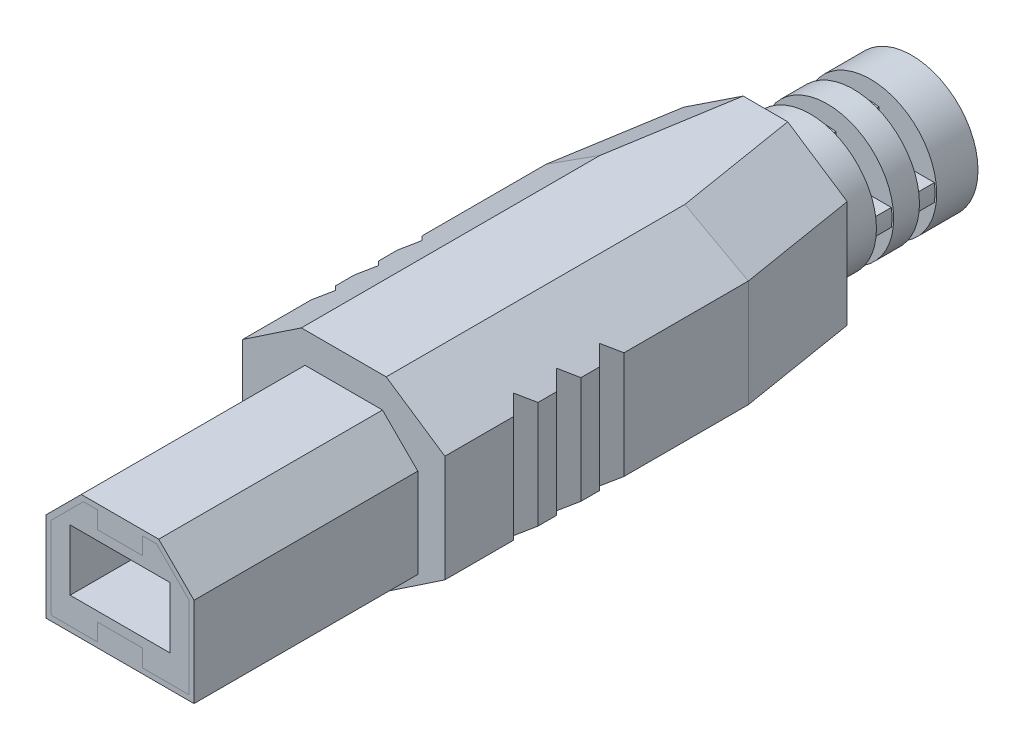
SolidWorks part; units mm, degrees
ref_plane "Front" through (0, 0, 0) normal (0, 0, 1) x (1, 0, 0)
ref_plane "Top" through (0, 0, 0) normal (0, 1, 0) x (1, 0, 0)
ref_plane "Right" through (0, 0, 0) normal (1, 0, 0) x (0, 0, -1)
sketch "Sketch1" plane through (0, 0, 0) normal (0, 0, 1) x (1, 0, 0)
  line L5 (0, 0) -> (-4.3, 0)
  line L6 (-4.3, 0) -> (-4.3, 5.2)
  line L10 (-4.3, 5.2) -> (-2.25, 7.25)
  line L11 (-2.25, 7.25) -> (0, 7.25)
  line L12 (0, 7.25) -> (0, 0)
  line L13 (0, 5.395) -> (-2.9, 5.395)
  line L14 (-2.9, 5.395) -> (-2.9, 1.855)
  line L15 (-2.9, 1.855) -> (0, 1.855)
  line L16 (0, 5.95) -> (-1.3, 5.95)
  line L17 (-1.3, 5.95) -> (-1.3, 6.95)
  line L18 (0, 1.3) -> (-1.3, 1.3)
  line L19 (-1.3, 1.3) -> (-1.3, 0.3)
  line L20 (-2.1257, 6.95) -> (-1.3, 6.95)
  line L21 (-0.3, 6.95) -> (-0.3, 0.3) construction
  line L22 (-1.3, 0.3) -> (-4, 0.3)
  line L23 (-4, 0.3) -> (-4, 5.0757)
  line L24 (-4, 5.0757) -> (-2.1257, 6.95)
  line L25 (-0.3, 0.3) -> (-4, 0.3) construction
  line L26 (-2.1257, 6.95) -> (-0.3, 6.95) construction
  line L27 (-1.3, 6.95) -> (-0.3, 6.95) construction
  line L28 (-1.3, 1.3) -> (-1.3, 1.855)
  line L29 (-0.3, 0.3) -> (-1.3, 0.3) construction
  line L31 (-1.3, 5.395) -> (-1.3, 5.95)
  dimension "D1" = 0.3
  dimension "D2" = 1.3
  dimension "D4" = 3.54
  dimension "D3" = 1.3
  dimension "D5" = 2.9
  dimension "D6" = 7.25
  dimension "D7" = 4.3
  dimension "D8" = 225
  dimension "D9" = 2.25
extrude "Boss-Extrude1" add sketch "Sketch1" against normal blind 13 contours L13 L31 L17 L20 L24 L23 L22 L19 L28 L15 L14 | L28 L18 L12 L15 | L23 L24 L20 L17 L16 L12 L11 L10 L6 L5 L18 L19 L22 | L31 L13 L12 L16
sketch "Sketch2" plane through (0, 0, 0) normal (0, 0, 1) x (1, 0, 0)
  line L0 (0, 5.95) -> (-1.3, 5.95)
  line L1 (-1.3, 5.95) -> (-1.3, 6.95)
  line L2 (-1.3, 6.95) -> (-2.1257, 6.95)
  line L3 (-2.1257, 6.95) -> (-4, 5.0757)
  line L4 (-4, 5.0757) -> (-4, 0.3)
  line L5 (-4, 0.3) -> (-1.3, 0.3)
  line L6 (-1.3, 0.3) -> (-1.3, 1.3)
  line L7 (-1.3, 1.3) -> (0, 1.3)
split line "Split Line4"
mirror "Mirror1" about plane through (0, 0, -13) normal (-1, 0, 0) of bodies 115
sketch "Sketch3" plane through (0, 0, -13) normal (0, 0, -1) x (-1, 0, 0)
  line L0 (-5.875, 7.125) -> (-3.0438, 9.025) construction
  line L1 (-3.0438, 9.025) -> (3.0438, 9.025)
  line L2 (-5.875, 7.125) -> (-5.875, 0.125)
  line L3 (-3.0438, -1.775) -> (3.0438, -1.775)
  line L4 (5.875, 7.125) -> (5.875, 0.125)
  line L5 (3.0438, 9.025) -> (5.875, 7.125) construction
  line L6 (5.875, 0.125) -> (3.0438, -1.775) construction
  line L7 (0, 0) -> (0, -1.775) construction
  line L8 (-3.0438, -1.775) -> (-5.875, 0.125) construction
  line L9 (0, 9.025) -> (0, 7.25)
  line L10 (-5.875, 7.125) -> (-5.875, 9.025)
  line L11 (2.25, 7.25) -> (-2.25, 7.25) construction
  line L12 (-5.875, 9.025) -> (-3.0438, 9.025)
  line L13 (3.0438, 9.025) -> (5.875, 9.025)
  line L14 (5.875, 9.025) -> (5.875, 7.125)
  line L15 (5.875, 0.125) -> (5.875, -1.775)
  line L16 (5.875, -1.775) -> (3.0438, -1.775)
  line L17 (-3.0438, -1.775) -> (-5.875, -1.775)
  line L18 (-5.875, -1.775) -> (-5.875, 0.125)
  line L19 (0, 7.25) -> (0, 3.625)
  line L20 (0, 3.625) -> (5.875, 3.625)
  line M13 (4.3, 0) -> (4.3, 5.2)
  line M14 (4.3, 5.2) -> (2.25, 7.25)
  line M15 (2.25, 7.25) -> (-2.25, 7.25)
  line M17 (-2.9, 5.395) -> (2.9, 5.395)
  line M18 (2.9, 5.395) -> (2.9, 1.855)
  dimension "D1" = 12.36
  dimension "D2" = 12.36
  dimension "D3" = 11.75
  dimension "D4" = 10.8
  dimension "D5" = 7
extrude "Boss-Extrude2" add sketch "Sketch3" along normal blind 24.5 contours L19 L20 M18 M17 | L20 L19 M18 M13 M14 M15 M17 | L20 L4 L14 L13 L1 L9 M13 M15 M14
sketch "Sketch4" plane through (0, 9.025, 0) normal (0, 1, 0) x (1, 0, 0)
  line L0 (0, 37.5) -> (0, 13) construction
  line L4 (-4.75, 37.5) -> (-5.875, 30.63)
  line L5 (-5.875, 37.5) -> (-5.875, 13) construction
  line L8 (-4.75, 37.5) -> (-5.875, 37.5)
  line L9 (-5.875, 37.5) -> (-5.875, 30.63)
  line L14 (-5.875, 23.4071) -> (-5.1679, 22.7)
  line L15 (-5.1679, 22.7) -> (-5.875, 21.9929)
  line L16 (-5.1679, 22.7) -> (-5.875, 22.7) construction
  line L17 (-5.875, 23.4071) -> (-5.875, 21.9929)
  line L18 (-5.1679, 20.2) -> (-5.875, 19.4929)
  line L19 (-5.875, 20.9071) -> (-5.1679, 20.2)
  line L20 (-5.875, 20.9071) -> (-5.875, 19.4929)
  line L21 (-5.1679, 17.7) -> (-5.875, 16.9929)
  line L22 (-5.875, 18.4071) -> (-5.1679, 17.7)
  line L23 (-5.875, 18.4071) -> (-5.875, 16.9929)
  line L34 (0, 37.5) -> (-5.875, 37.5) construction
  dimension "D1" = 17.63
  dimension "D2" = 4.75
  dimension "D3" = 1
  dimension "D4" = 9.7
  dimension "D6" = 2.5
  dimension "D5" = 3
extrude "Cut-Extrude1" cut sketch "Sketch4" against normal through all
chamfer "Chamfer1" distance 3.41 angle 33.86 3 edges at (-5.875, 9.025, -14.9964) (-5.875, 9.025, -27.0186) (-5.3125, 9.025, -34.065)
ref_plane "Plane1" through (0, 0, -13) normal (0, 0, 1) x (1, 0, 0)
split "Split1" trim tools "Plane1" bodies to split 118 resulting bodies 120 121
ref_plane "Plane2" through (0, 3.625, 0) normal (0, -1, 0) x (-1, 0, 0)
mirror "Mirror9" about plane through (0, 0, -37.5) normal (-1, 0, 0) of bodies 121
mirror "Mirror10" about plane through (0, 3.625, -37.5) normal (0, 1, 0) of bodies 122
combine bodies "Combine1" operation type add bodies to combine 123 120
sketch "Sketch7" plane through (0, 3.625, 0) normal (0, 1, 0) x (1, 0, 0)
  line L0 (0, 37.5) -> (0, 40.1)
  line L1 (1.2946, 37.5) -> (-1.2946, 37.5) construction
  line L2 (0, 37.5) -> (3.85, 37.5)
  line L3 (3.85, 37.5) -> (3.85, 40.1)
  line L4 (3.85, 40.1) -> (0, 40.1)
  line L5 (0, 41.1) -> (3.85, 41.1)
  line L6 (3.85, 41.1) -> (3.85, 42.6)
  line L7 (3.85, 42.6) -> (0, 42.6)
  line L8 (0, 43.6) -> (3.85, 43.6)
  line L9 (3.85, 43.6) -> (3.85, 46)
  line L10 (3.85, 46) -> (0, 46)
  line L11 (3.85, 43.6) -> (3.85, 42.6) construction
  line L12 (3.85, 41.1) -> (3.85, 40.1) construction
  line L13 (0, 43.6) -> (0, 46)
  line L14 (0, 41.1) -> (0, 42.6)
  dimension "D1" = 2.6
  dimension "D2" = 1.5
  dimension "D3" = 2.4
  dimension "D4" = 1
  dimension "D5" = 3.85
revolve "Revolve1" add sketch "Sketch7" angle 360 about L13
sketch "Sketch5" plane through (0, 0, -37.5) normal (0, 0, -1) x (-1, 0, 0)
  line L0 (0, 3.625) -> (0, 6.375) construction
  line L1 (-4.75, 6.737) -> (4.75, 6.737) construction
  line L2 (-4.75, 6.737) -> (-4.75, 0.513) construction
  line L3 (-4.75, 0.513) -> (4.75, 0.513) construction
  line L4 (4.75, 6.737) -> (4.75, 0.513) construction
  line L5 (-4.75, 6.737) -> (4.75, 0.513) construction
  line L6 (-4.75, 0.513) -> (4.75, 6.737) construction
  line L7 (-0.5, 6.3292) -> (-0.5, 4.125)
  line L8 (-0.5, 4.125) -> (-3.7165, 4.125)
  line L9 (0, 3.625) -> (-3.75, 3.625) construction
  line L10 (-0.5, 4.125) -> (0, 4.125) construction
  line L12 (-0.5, 3.625) -> (-0.5, 4.125) construction
  line L13 (0.5, 4.125) -> (3.7165, 4.125)
  line L14 (0.5, 6.3292) -> (0.5, 4.125)
  line L15 (0.5, 3.125) -> (3.7165, 3.125)
  line L16 (0.5, 0.9208) -> (0.5, 3.125)
  line L17 (-0.5, 0.9208) -> (-0.5, 3.125)
  line L18 (-0.5, 3.125) -> (-3.7165, 3.125)
  arc A0 (0.5, 6.3292) -> (-0.5, 6.3292) centre (0, 3.625) ccw
  arc A1 (-3.7165, 4.125) -> (-3.7165, 3.125) centre (0, 3.625) ccw
  arc A2 (3.7165, 4.125) -> (3.7165, 3.125) centre (0, 3.625) cw
  arc A3 (0.5, 0.9208) -> (-0.5, 0.9208) centre (0, 3.625) cw
  point P0 (0, 3.625)
  dimension "D2" = 3.75
  dimension "D3" = 2.75
  dimension "D1" = 0.5
extrude "Boss-Extrude3" add sketch "Sketch5" along normal blind 6.25
